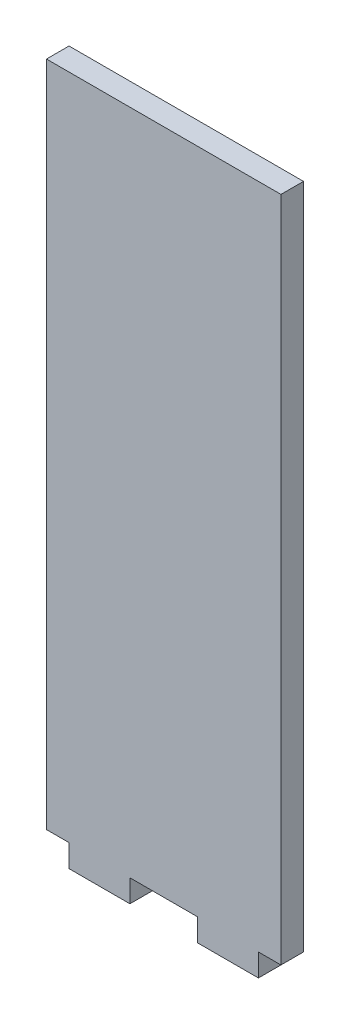
SolidWorks part; units mm, degrees
ref_plane "Front Plane" through (0, 0, 0) normal (0, 0, 1) x (1, 0, 0)
ref_plane "Top Plane" through (0, 0, 0) normal (0, 1, 0) x (1, 0, 0)
ref_plane "Right Plane" through (0, 0, 0) normal (1, 0, 0) x (0, 0, -1)
sketch "Sketch2" plane through (0, 0, 0) normal (0, 0, 1) x (1, 0, 0)
  line L0 (9.525, -93.98) -> (9.525, -100.33)
  line L1 (-33.02, 93.98) -> (33.02, 93.98)
  line L2 (-33.02, 93.98) -> (-33.02, -93.98)
  line L3 (-33.02, -93.98) -> (33.02, -93.98)
  line L4 (33.02, 93.98) -> (33.02, -93.98)
  line L5 (-26.67, -93.98) -> (-9.525, -93.98)
  line L6 (-26.67, -93.98) -> (-26.67, -100.33)
  line L7 (-26.67, -100.33) -> (-9.525, -100.33)
  line L8 (-9.525, -93.98) -> (-9.525, -100.33)
  line L9 (9.525, -100.33) -> (26.67, -100.33)
  line L10 (26.67, -93.98) -> (26.67, -100.33)
  line L11 (-26.67, -93.98) -> (9.525, -93.98) construction
  point P4 (0, 93.98)
  point P6 (33.02, 0)
  dimension "D1" = 187.96
  dimension "D2" = 66.04
  dimension "D3" = 6.35
  dimension "D4" = 6.35
  dimension "D5" = 17.145
  dimension "D7" = 36.195
  dimension "D6" = 2
extrude "Boss-Extrude1" add sketch "Sketch2" along normal blind 6.35 contours L4 L1 L2 L3 | L8 L3 L6 L7 | L10 L3 L0 L9 region at (18.0975, -97.155, 0) region at (0, 0, 0) region at (-18.0975, -97.155, 0)
